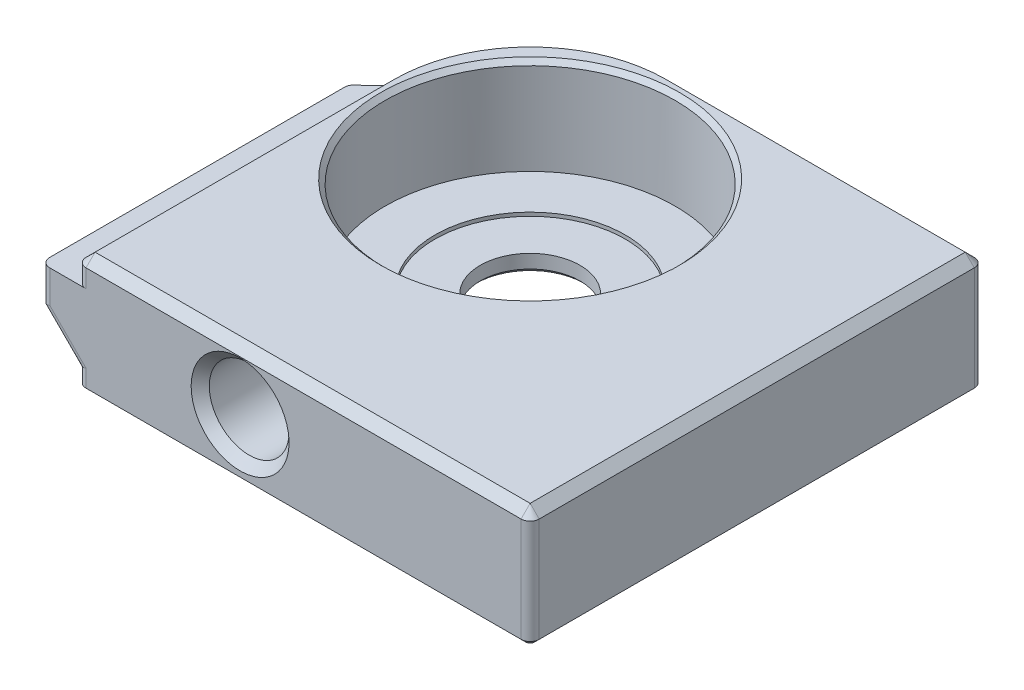
SolidWorks part; units mm, degrees
ref_plane "Front Plane" through (0, 0, 0) normal (0, 0, 1) x (1, 0, 0)
ref_plane "Top Plane" through (0, 0, 0) normal (0, 1, 0) x (1, 0, 0)
ref_plane "Right Plane" through (0, 0, 0) normal (1, 0, 0) x (0, 0, -1)
sketch "Sketch1" plane through (0, 0, 0) normal (0, 1, 0) x (1, 0, 0)
  line L1 (-12.5, -12.5) -> (12.5, -12.5)
  line L2 (-12.5, -12.5) -> (-12.5, 12.5)
  line L3 (-12.5, 12.5) -> (12.5, 12.5)
  line L4 (12.5, -12.5) -> (12.5, 12.5)
  line L5 (-12.5, -12.5) -> (12.5, 12.5) construction
  line L6 (-12.5, 12.5) -> (12.5, -12.5) construction
  point P0 (0, 0)
  dimension "D1" = 25
  dimension "D2" = 25
extrude "Boss-Extrude1" add sketch "Sketch1" along normal blind 6.5
sketch "Sketch2" plane through (0, 6.5, 0) normal (0, 1, 0) x (1, 0, 0)
  line L0 (-3.5, 3.5) -> (-12.5, 3.5) construction
  line L2 (-12.5, 12.5) -> (-3.3082, 3.3082) construction
  line L3 (12.5, 12.5) -> (-12.5, 12.5) construction
  line L4 (-12.5, 12.5) -> (-12.5, -12.5) construction
  circle A0 centre (-3.5, 3.5) radius 8
  dimension "D1" = 16
  dimension "D2" = 45
  dimension "D3" = 9
extrude "Cut-Extrude1" cut sketch "Sketch2" against normal blind 5.5
fillet "Fillet1" radius 8 1 edges at (-12.5, 3.25, -12.5)
sketch "Sketch4" plane through (0, 0, 12.5) normal (0, 0, 1) x (1, 0, 0)
  line L0 (-3.5, 6.5) -> (-3.5, 0) construction
  line L1 (-12.5, 0) -> (12.5, 0) construction
  line L2 (-12.5, 6.5) -> (-12.5, 0) construction
  line L3 (-12.5, 6.5) -> (12.5, 6.5) construction
  circle A0 centre (-3.5, 3.25) radius 2.2
  dimension "D2" = 4.4
  dimension "D1" = 9
extrude "Cut-Extrude2" cut sketch "Sketch4" against normal blind 7.5
sketch "Sketch5" plane through (0, 0, 12.5) normal (0, 0, 1) x (1, 0, 0)
  line L0 (-12.25, 3) -> (-17.5409, 3) construction
  line L1 (-12.5, 6.5) -> (-12.5, 0) construction
  line L2 (-12.5, 1) -> (-14.5, 3)
  line L3 (-14.5, 3) -> (-14.5, 5)
  line L4 (-14.5, 5) -> (-12.5, 5)
  line L5 (-12.5, 1) -> (-12.5, 5)
  line L6 (-12.5, 6.5) -> (12.5, 6.5) construction
  line L7 (-12.5, 0) -> (12.5, 0) construction
  dimension "D1" = 45
  dimension "D2" = 1.5
  dimension "D3" = 1
  dimension "D4" = 2
extrude "Boss-Extrude2" add sketch "Sketch5" against normal up to vertex (17 mm away)
fillet "Fillet2" radius 10 1 edges at (-12.5, 3, -4.5)
sketch "Sketch6" plane through (0, 1, 0) normal (0, 1, 0) x (1, 0, 0)
  circle A0 centre (-3.5, 3.5) radius 2.75
  dimension "D1" = 5.5
extrude "Cut-Extrude3" cut sketch "Sketch6" against normal through all
sketch "Sketch7" plane through (0, 1, 0) normal (0, 1, 0) x (1, 0, 0)
  circle A0 centre (-3.5, 3.5) radius 8
  circle A1 centre (-3.5, 3.5) radius 5.25
  circle A2 centre (-3.5, 3.5) radius 8 construction
  dimension "D1" = 10.5
extrude "Boss-Extrude3" add sketch "Sketch7" along normal blind 0.2
fillet "Fillet3" radius 0.5 7 edges at (-14.5, 4, -4.5) (-12.5, 0.5, 12.5) (-13.5, 2, 12.5) (-14.5, 4, 12.5) (-12.5, 5.75, 12.5) (12.5, 3.25, -12.5) (12.5, 3.25, 12.5)
chamfer "Chamfer1" distance 0.5 angle 45 9 edges at (-12.5, 6.5, 3.75) (-1.3, 3.25, 12.5) (3.75, 6.5, -12.5) (-10.1569, 6.5, -10.1569) (12.5, 6.5, 0) (0, 6.5, 12.5) (12.3536, 6.5, -12.3536) (12.3536, 6.5, 12.3536) (-12.3536, 6.5, 12.3536)
chamfer "Chamfer7" distance 0.25 angle 45 6 edges at (-3.5, 0, -0.75) (-12.5, 0, 3.75) (0, 0, 12.5) (12.5, 0, 0) (3.75, 0, -12.5) (-3.5, 6.5, 4.5)
